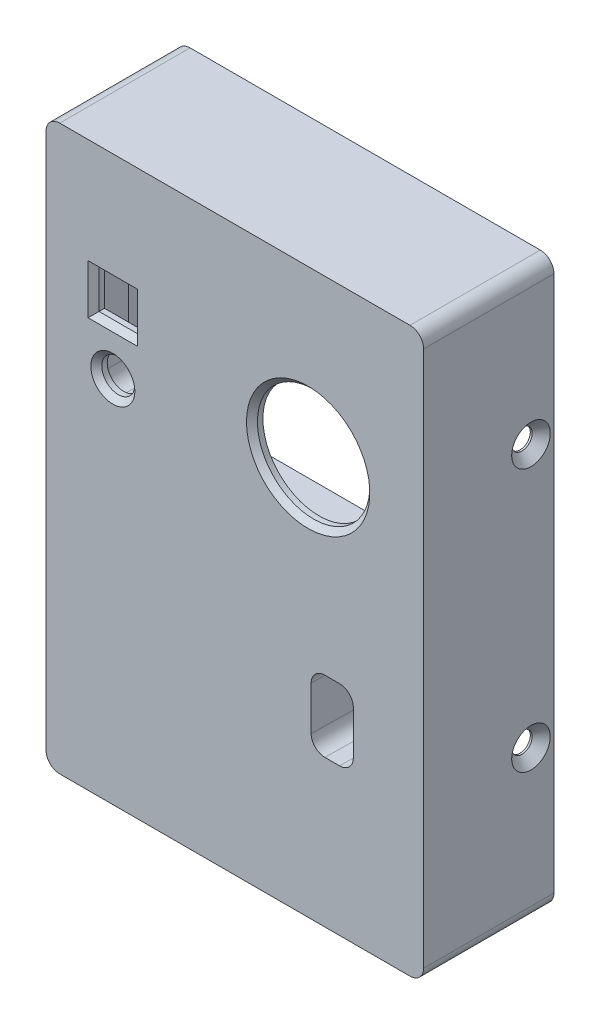
SolidWorks part; units mm, degrees
ref_plane "Front Plane" through (0, 0, 0) normal (0, 0, 1) x (1, 0, 0)
ref_plane "Top Plane" through (0, 0, 0) normal (0, 1, 0) x (1, 0, 0)
ref_plane "Right Plane" through (0, 0, 0) normal (1, 0, 0) x (0, 0, -1)
sketch "Sketch2" plane through (0, 0, 0) normal (0, 0, 1) x (1, 0, 0)
  line L5 (-34.5, -73.3) -> (34.5, -73.3)
  line L6 (-34.5, -73.3) -> (-34.5, 29.7)
  line L7 (-34.5, 29.7) -> (34.5, 29.7)
  line L8 (34.5, -73.3) -> (34.5, 29.7)
extrude "Boss-Extrude1" add sketch "Sketch2" along normal blind 2
sketch "Sketch3" plane through (0, 0, 0) normal (0, 0, -1) x (-1, 0, 0)
  line L1 (34.5, 29.7) -> (-34.5, 29.7)
  line L2 (34.5, 29.7) -> (34.5, -73.3)
  line L3 (34.5, -73.3) -> (-34.5, -73.3)
  line L4 (-34.5, 29.7) -> (-34.5, -73.3)
  line L12 (32.5, -71.3) -> (32.5, 27.7)
  line L13 (32.5, 27.7) -> (-32.5, 27.7)
  line L14 (-32.5, 27.7) -> (-32.5, -71.3)
  line L15 (-32.5, -71.3) -> (32.5, -71.3)
  line L16 (32.5, -71.3) -> (32.5, 27.7)
  line L17 (32.5, 27.7) -> (-32.5, 27.7)
  line L18 (-32.5, 27.7) -> (-32.5, -71.3)
  line L19 (-32.5, -71.3) -> (32.5, -71.3)
  dimension "D1" = 2
extrude "Boss-Extrude2" add sketch "Sketch3" along normal up to surface (21.816 mm away)
sketch "Sketch4" plane through (0, 0, 0) normal (0, 0, -1) x (-1, 0, 0)
  line L0 (26.2, -13.3) -> (18.3635, -13.3) construction
  line L1 (15.8263, -13.3) -> (18.3635, -13.3) construction
  line L2 (15.8263, -13.3) -> (13.1504, -13.3) construction
  line L3 (10.0494, -13.3) -> (13.1504, -13.3) construction
  line L4 (10.0494, -13.3) -> (-0.8511, -13.3) construction
  line L5 (-3.379, -13.3) -> (-0.8511, -13.3) construction
  line L6 (-3.379, -13.3) -> (-11.0624, -13.3) construction
  line L7 (-13.1307, -13.3) -> (-11.0624, -13.3) construction
  line L8 (-13.1307, -13.3) -> (-21.9, -13.3) construction
  line L9 (-26.2, -8.9391) -> (-26.2, -8.1901) construction
  line L10 (-26.2, -6.895) -> (-26.2, -8.1901) construction
  line L11 (-26.2, -6.895) -> (-26.2, -2.3887) construction
  line L12 (-26.2, -1.2629) -> (-26.2, -2.3887) construction
  line L13 (-26.2, -1.2629) -> (-26.2, 3.2404) construction
  line L14 (-26.2, 8) -> (-26.2, 3.2404) construction
  line L15 (-21.9, 12.3) -> (-13.1307, 12.3) construction
  line L16 (-11.0624, 12.3) -> (-13.1307, 12.3) construction
  line L17 (-11.0624, 12.3) -> (-3.379, 12.3) construction
  line L18 (-0.8511, 12.3) -> (-3.379, 12.3) construction
  line L19 (-0.8511, 12.3) -> (10.0494, 12.3) construction
  line L20 (13.1504, 12.3) -> (10.0494, 12.3) construction
  line L21 (13.1504, 12.3) -> (15.8263, 12.3) construction
  line L22 (18.3635, 12.3) -> (15.8263, 12.3) construction
  line L23 (18.3635, 12.3) -> (26.2, 12.3) construction
  line L24 (29, 9.5) -> (29, 8.1768) construction
  line L25 (29, 3.2404) -> (29, 8.1768) construction
  line L26 (29, 3.2404) -> (29, -1.2629) construction
  line L27 (29, -2.3887) -> (29, -1.2629) construction
  line L28 (29, -2.3887) -> (29, -6.895) construction
  line L29 (29, -8.1901) -> (29, -6.895) construction
  line L30 (29, -8.1901) -> (29, -8.9391) construction
  line L31 (29, -10.5) -> (29, -8.9391) construction
  line L32 (26.2, -13.3) -> (18.3635, -13.3) construction
  line L33 (15.8263, -13.3) -> (18.3635, -13.3) construction
  line L34 (15.8263, -13.3) -> (13.1504, -13.3) construction
  line L35 (10.0494, -13.3) -> (13.1504, -13.3) construction
  line L36 (10.0494, -13.3) -> (-0.8511, -13.3) construction
  line L37 (-3.379, -13.3) -> (-0.8511, -13.3) construction
  line L38 (-3.379, -13.3) -> (-11.0624, -13.3) construction
  line L39 (-13.1307, -13.3) -> (-11.0624, -13.3) construction
  line L40 (-13.1307, -13.3) -> (-21.9, -13.3) construction
  line L41 (-26.2, -8.9391) -> (-26.2, -8.1901) construction
  line L42 (-26.2, -6.895) -> (-26.2, -8.1901) construction
  line L43 (-26.2, -6.895) -> (-26.2, -2.3887) construction
  line L44 (-26.2, -1.2629) -> (-26.2, -2.3887) construction
  line L45 (-26.2, -1.2629) -> (-26.2, 3.2404) construction
  line L46 (-26.2, 8) -> (-26.2, 3.2404) construction
  line L47 (-21.9, 12.3) -> (-13.1307, 12.3) construction
  line L48 (-11.0624, 12.3) -> (-13.1307, 12.3) construction
  line L49 (-11.0624, 12.3) -> (-3.379, 12.3) construction
  line L50 (-0.8511, 12.3) -> (-3.379, 12.3) construction
  line L51 (-0.8511, 12.3) -> (10.0494, 12.3) construction
  line L52 (13.1504, 12.3) -> (10.0494, 12.3) construction
  line L53 (13.1504, 12.3) -> (15.8263, 12.3) construction
  line L54 (18.3635, 12.3) -> (15.8263, 12.3) construction
  line L55 (18.3635, 12.3) -> (26.2, 12.3) construction
  line L56 (29, 9.5) -> (29, 8.1768) construction
  line L57 (29, 3.2404) -> (29, 8.1768) construction
  line L58 (29, 3.2404) -> (29, -1.2629) construction
  line L59 (29, -2.3887) -> (29, -1.2629) construction
  line L60 (29, -2.3887) -> (29, -6.895) construction
  line L61 (29, -8.1901) -> (29, -6.895) construction
  line L62 (29, -8.1901) -> (29, -8.9391) construction
  line L63 (29, -10.5) -> (29, -8.9391) construction
  line L64 (-26.2, -8.9391) -> (-26.2, -9) construction
  line L65 (-26.2, -8.9391) -> (-26.2, -9) construction
  line L66 (26.2, -13.25) -> (18.3635, -13.25)
  line L67 (15.8263, -13.25) -> (18.3635, -13.25)
  line L68 (15.8263, -13.25) -> (13.1504, -13.25)
  line L69 (10.0494, -13.25) -> (13.1504, -13.25)
  line L70 (10.0494, -13.25) -> (-0.8511, -13.25)
  line L71 (-3.379, -13.25) -> (-0.8511, -13.25)
  line L72 (-3.379, -13.25) -> (-11.0624, -13.25)
  line L73 (-13.1307, -13.25) -> (-11.0624, -13.25)
  line L74 (-13.1307, -13.25) -> (-21.9, -13.25)
  line L75 (-26.15, -8.9391) -> (-26.15, -9)
  line L76 (-26.15, -8.9391) -> (-26.15, -8.1901)
  line L77 (-26.15, -6.895) -> (-26.15, -8.1901)
  line L78 (-26.15, -6.895) -> (-26.15, -2.3887)
  line L79 (-26.15, -1.2629) -> (-26.15, -2.3887)
  line L80 (-26.15, -1.2629) -> (-26.15, 3.2404)
  line L81 (-26.15, 8) -> (-26.15, 3.2404)
  line L82 (-21.9, 12.25) -> (-13.1307, 12.25)
  line L83 (-11.0624, 12.25) -> (-13.1307, 12.25)
  line L84 (-11.0624, 12.25) -> (-3.379, 12.25)
  line L85 (-0.8511, 12.25) -> (-3.379, 12.25)
  line L86 (-0.8511, 12.25) -> (10.0494, 12.25)
  line L87 (13.1504, 12.25) -> (10.0494, 12.25)
  line L88 (13.1504, 12.25) -> (15.8263, 12.25)
  line L89 (18.3635, 12.25) -> (15.8263, 12.25)
  line L90 (18.3635, 12.25) -> (26.2, 12.25)
  line L91 (28.95, 9.5) -> (28.95, 8.1768)
  line L92 (28.95, 3.2404) -> (28.95, 8.1768)
  line L93 (28.95, 3.2404) -> (28.95, -1.2629)
  line L94 (28.95, -2.3887) -> (28.95, -1.2629)
  line L95 (28.95, -2.3887) -> (28.95, -6.895)
  line L96 (28.95, -8.1901) -> (28.95, -6.895)
  line L97 (28.95, -8.1901) -> (28.95, -8.9391)
  line L98 (28.95, -10.5) -> (28.95, -8.9391)
  line L99 (30.45, -10.5) -> (30.45, -8.9391)
  line L100 (30.45, -8.1901) -> (30.45, -8.9391)
  line L101 (30.45, -8.1901) -> (30.45, -6.895)
  line L102 (30.45, -2.3887) -> (30.45, -6.895)
  line L103 (30.45, -2.3887) -> (30.45, -1.2629)
  line L104 (30.45, 3.2404) -> (30.45, -1.2629)
  line L105 (30.45, 3.2404) -> (30.45, 8.1768)
  line L106 (30.45, 9.5) -> (30.45, 8.1768)
  line L107 (18.3635, 13.75) -> (26.2, 13.75)
  line L108 (18.3635, 13.75) -> (15.8263, 13.75)
  line L109 (13.1504, 13.75) -> (15.8263, 13.75)
  line L110 (13.1504, 13.75) -> (10.0494, 13.75)
  line L111 (-0.8511, 13.75) -> (10.0494, 13.75)
  line L112 (-0.8511, 13.75) -> (-3.379, 13.75)
  line L113 (-11.0624, 13.75) -> (-3.379, 13.75)
  line L114 (-11.0624, 13.75) -> (-13.1307, 13.75)
  line L115 (-21.9, 13.75) -> (-13.1307, 13.75)
  line L116 (-27.65, 8) -> (-27.65, 3.2404)
  line L117 (-27.65, -1.2629) -> (-27.65, 3.2404)
  line L118 (-27.65, -1.2629) -> (-27.65, -2.3887)
  line L119 (-27.65, -6.895) -> (-27.65, -2.3887)
  line L120 (-27.65, -6.895) -> (-27.65, -8.1901)
  line L121 (-27.65, -8.9391) -> (-27.65, -8.1901)
  line L122 (-27.65, -8.9391) -> (-27.65, -9)
  line L123 (-13.1307, -14.75) -> (-21.9, -14.75)
  line L124 (-13.1307, -14.75) -> (-11.0624, -14.75)
  line L125 (-3.379, -14.75) -> (-11.0624, -14.75)
  line L126 (-3.379, -14.75) -> (-0.8511, -14.75)
  line L127 (10.0494, -14.75) -> (-0.8511, -14.75)
  line L128 (10.0494, -14.75) -> (13.1504, -14.75)
  line L129 (15.8263, -14.75) -> (13.1504, -14.75)
  line L130 (15.8263, -14.75) -> (18.3635, -14.75)
  line L131 (26.2, -14.75) -> (18.3635, -14.75)
  arc A0 (-25.8255, -10.7551) -> (-21.9, -13.3) centre (-21.9, -9) ccw construction
  arc A1 (-26.2, -9) -> (-25.8255, -10.7551) centre (-21.9, -9) ccw construction
  arc A2 (-21.9, 12.3) -> (-26.1958, 8.19) centre (-21.9, 8) ccw construction
  arc A3 (29, 9.5) -> (26.2, 12.3) centre (26.2, 9.5) ccw construction
  arc A4 (26.2, -13.3) -> (28.9961, -10.6486) centre (26.2, -10.5) ccw construction
  arc A5 (-25.8255, -10.7551) -> (-21.9, -13.3) centre (-21.9, -9) ccw construction
  arc A6 (-26.2, -9) -> (-25.8255, -10.7551) centre (-21.9, -9) ccw construction
  arc A7 (-21.9, 12.3) -> (-26.1958, 8.19) centre (-21.9, 8) ccw construction
  arc A8 (29, 9.5) -> (26.2, 12.3) centre (26.2, 9.5) ccw construction
  arc A9 (26.2, -13.3) -> (28.9961, -10.6486) centre (26.2, -10.5) ccw construction
  arc A10 (28.9961, -10.6486) -> (29, -10.5) centre (26.2, -10.5) ccw construction
  arc A11 (28.9961, -10.6486) -> (29, -10.5) centre (26.2, -10.5) ccw construction
  arc A12 (-26.1958, 8.19) -> (-26.2, 8) centre (-21.9, 8) ccw construction
  arc A13 (-26.1958, 8.19) -> (-26.2, 8) centre (-21.9, 8) ccw construction
  arc A14 (-25.7799, -10.7347) -> (-21.9, -13.25) centre (-21.9, -9) ccw
  arc A15 (-26.15, -9) -> (-25.7799, -10.7347) centre (-21.9, -9) ccw
  arc A16 (-26.1458, 8.1878) -> (-26.15, 8) centre (-21.9, 8) ccw
  arc A17 (-21.9, 12.25) -> (-26.1458, 8.1878) centre (-21.9, 8) ccw
  arc A18 (28.95, 9.5) -> (26.2, 12.25) centre (26.2, 9.5) ccw
  arc A19 (28.9461, -10.6459) -> (28.95, -10.5) centre (26.2, -10.5) ccw
  arc A20 (26.2, -13.25) -> (28.9461, -10.6459) centre (26.2, -10.5) ccw
  arc A21 (30.45, 9.5) -> (26.2, 13.75) centre (26.2, 9.5) ccw
  arc A22 (-21.9, 13.75) -> (-27.6444, 8.2541) centre (-21.9, 8) ccw
  arc A23 (-27.6444, 8.2541) -> (-27.65, 8) centre (-21.9, 8) ccw
  arc A24 (-27.65, -9) -> (-27.1492, -11.347) centre (-21.9, -9) ccw
  arc A25 (-27.1492, -11.347) -> (-21.9, -14.75) centre (-21.9, -9) ccw
  arc A26 (26.2, -14.75) -> (30.444, -10.7255) centre (26.2, -10.5) ccw
  arc A27 (30.444, -10.7255) -> (30.45, -10.5) centre (26.2, -10.5) ccw
  dimension "D1" = 0.05
  dimension "D2" = 1.5
extrude "Boss-Extrude3" add sketch "Sketch4" along normal blind 7.5
sketch "Sketch7" plane through (0, 0, 0) normal (0, 0, -1) x (-1, 0, 0)
  line L2 (25.821, 9.521) -> (18.779, 9.521)
  line L3 (25.821, 9.521) -> (25.821, 2.479)
  line L4 (25.821, 2.479) -> (18.779, 2.479)
  line L5 (18.779, 9.521) -> (18.779, 2.479)
  circle A0 centre (-13.4, -0.5) radius 10.271
  arc A1 (-4.343, -5.3441) -> (-10.2819, 9.2863) centre (-13.4, -0.5) ccw construction
  circle A2 centre (22.3, -5.9) radius 3.021
  arc A3 (22.3, -8.921) -> (22.3, -2.879) centre (22.3, -5.9) ccw construction
extrude "Cut-Extrude1" cut sketch "Sketch7" against normal through all
sketch "Sketch9" plane through (0, 0, 0) normal (0, 0, -1) x (-1, 0, 0)
  line L0 (-32.5, -71.3) -> (32.5, -71.3) construction
  line L1 (-25, -71.3) -> (-21.5, -71.3)
  line L2 (-25, -71.3) -> (-25, -61.3)
  line L3 (-25, -61.3) -> (-21.5, -61.3)
  line L4 (-21.5, -71.3) -> (-21.5, -61.3)
  line L5 (-23, -33.3) -> (-23, -68.3) construction
  line L6 (-23, -68.3) -> (-23, -61.3)
  line L7 (24, -70.3) -> (20.5, -70.3)
  line L9 (-23, -68.3) -> (-21.5, -68.3)
  line L10 (-23, -68.3) -> (22, -68.3) construction
  line L11 (24, -70.3) -> (24, -59.475)
  line L12 (24, -59.475) -> (20.5, -59.475)
  line L13 (20.5, -70.3) -> (20.5, -59.475)
  line L14 (27.075, -59.5) -> (10.475, -59.5) construction
  line L16 (22, -68.3) -> (22, -33.3) construction
  line L17 (20.5, -68.3) -> (22, -68.3)
  line L18 (22, -68.3) -> (22, -59.475)
  line M17 (-32.5, -71.3) -> (32.5, -71.3)
  dimension "D1" = 2
  dimension "D2" = 3.5
  dimension "D3" = 2
  dimension "D4" = 3.5
  dimension "D5" = 10
  dimension "D6" = 2
  dimension "D7" = 0.025
extrude "Boss-Extrude4" add sketch "Sketch9" along normal up to surface (19.69 mm away) contours L17 L18 L12 L13 | L9 L4 L3 region at (22.25, -64.8, 0) region at (-21.25, -63.8875, 0)
extrude "Boss-Extrude5" add sketch "Sketch9<4>" along normal up to surface (21.3 mm away) contours L18 L17 L13 L11 L12 M17 | L9 L3 L2 L4 M17 region at (23.6786, -66.9429, 0) region at (-22.787, -65.4245, 0)
sketch "Sketch9<4>" plane through (0, 0, 0) normal (0, 0, -1) x (-1, 0, 0) same geometry as "Sketch9"
sketch "Sketch10" plane through (0, 0, 0) normal (0, 0, -1) x (-1, 0, 0)
  line L1 (22, -68.3) -> (22, -33.3) construction
  line L2 (20.975, -34.1125) -> (20.975, -34.4125) construction
  line L3 (22, -46.325) -> (24, -46.325)
  line L7 (10.25, -34.1125) -> (10.25, -31.3)
  line L9 (20.95, -34.1125) -> (10.25, -34.1125)
  line L10 (10.25, -34.1125) -> (10.25, -38.2125)
  line L11 (10.25, -38.2125) -> (20.95, -38.2125)
  line L12 (20.95, -38.2125) -> (20.95, -34.1125)
  line L16 (22, -38.2125) -> (20.95, -38.2125)
  line L18 (22, -33.3) -> (-23, -33.3) construction
  line L21 (20.95, -34.1125) -> (20.95, -31.3)
  line L22 (20.95, -31.3) -> (24, -31.3)
  line L24 (22, -46.325) -> (22, -38.2125)
  line L25 (22, -33.3) -> (22, -38.2125)
  line L26 (22, -33.3) -> (20.95, -33.3)
  line L27 (24, -31.3) -> (24, -46.325)
  line L29 (10.25, -31.3) -> (5.25, -31.3)
  line L30 (5.25, -31.3) -> (5.25, -38.2125)
  line L31 (5.25, -38.2125) -> (10.25, -38.2125)
  line L32 (10.25, -33.3) -> (5.25, -33.3)
  line L33 (10.475, -46.3) -> (27.075, -46.3) construction
  line L34 (10.225, -34.4125) -> (10.225, -37.7125) construction
  point P27 (0, 0)
  dimension "D1" = 2
  dimension "D2" = 2
  dimension "D3" = 2
  dimension "D4" = 0.025
  dimension "D5" = 0.025
  dimension "D6" = 0.025
  dimension "D7" = 5
  dimension "D8" = 4.9125
  dimension "D9" = 4.1
extrude "Boss-Extrude6" add sketch "Sketch10" along normal up to surface (15.33 mm away) contours L11 L12 L9 L10 region at (-15.6, -36.1625, 0)
extrude "Boss-Extrude7" add sketch "Sketch10<4>" along normal up to surface (19.69 mm away) contours L25 L26 L21 L12 L16 | L7 L32 L30 L31 L10 region at (-21.475, -35.7562, 0) region at (-7.75, -35.7562, 0)
sketch "Sketch10<4>" plane through (0, 0, 0) normal (0, 0, -1) x (-1, 0, 0) same geometry as "Sketch10"
extrude "Boss-Extrude8" add sketch "Sketch10<6>" along normal up to surface (21.3 mm away) contours L32 L7 L29 L30 | L27 L22 L21 L26 L25 L24 L3 region at (-22.9004, -38.3871, 0) region at (-7.75, -32.3, 0)
sketch "Sketch10<6>" plane through (0, 0, 0) normal (0, 0, -1) x (-1, 0, 0) same geometry as "Sketch10"
sketch "Sketch11" plane through (0, 0, 0) normal (0, 0, -1) x (-1, 0, 0)
  line L0 (-16.63, -39.95) -> (-19.17, -39.95) construction
  line L1 (-14.15, -33.45) -> (-21.65, -33.45)
  line L2 (-14.15, -33.45) -> (-14.15, -46.45)
  line L3 (-14.15, -46.45) -> (-21.65, -46.45)
  line L4 (-21.65, -33.45) -> (-21.65, -46.45)
  line L5 (-17.9, -44.11) -> (-17.9, -35.79) construction
  line L6 (-16.63, -38.9) -> (-16.63, -41) construction
  line L8 (-19.17, -41) -> (-19.17, -38.9) construction
  line L9 (-17.63, -44.11) -> (-18.17, -44.11) construction
  line L10 (-18.17, -35.79) -> (-17.63, -35.79) construction
  point P23 (-17.9, -46.45)
  point P24 (-14.15, -39.95)
  dimension "D1" = 7.5
  dimension "D2" = 13
extrude "Cut-Extrude2" cut sketch "Sketch11" against normal through all
fillet "Fillet2" radius 2.5 4 edges at (34.5, 29.7, -9.908) (34.5, -73.3, -9.908) (-34.5, -73.3, -9.908) (-34.5, 29.7, -9.908)
chamfer "Chamfer1" distance 1 angle 45 6 edges at (-25.321, -5.9, 2) (-22.3, 2.479, 2) (-25.821, 6, 2) (-18.779, 6, 2) (-22.3, 9.521, 2) (3.129, -0.5, 2)
sketch "Sketch12" plane through (0, -73.3, 0) normal (0, -1, 0) x (1, 0, 0)
  line L0 (32, -21.816) -> (-32, -21.816) construction
  line L1 (-23.8601, -21.816) -> (-22.8601, -21.816)
  line L2 (-23.8601, -21.816) -> (-23.8601, -9.908)
  line L3 (-23.8601, -9.908) -> (-22.8601, -9.908)
  line L4 (-22.8601, -21.816) -> (-22.8601, -9.908)
  line L5 (-32, 2) -> (-32, -21.816) construction
  line L6 (-12.8601, -21.816) -> (-11.8601, -21.816)
  line L7 (-12.8601, -21.816) -> (-12.8601, -9.908)
  line L8 (-12.8601, -9.908) -> (-11.8601, -9.908)
  line L9 (-11.8601, -21.816) -> (-11.8601, -9.908)
  point P12 (-32, -9.908)
  dimension "D1" = 1
  dimension "D2" = 1
  dimension "D3" = 10
extrude "Cut-Extrude3" cut sketch "Sketch12" against normal up to next
sketch "Sketch13" plane through (0, 0, 0) normal (0, 0, -1) x (-1, 0, 0)
  line L1 (-14.15, -33.45) -> (-21.65, -33.45)
  line L2 (-14.15, -33.45) -> (-14.15, -46.45)
  line L3 (-14.15, -46.45) -> (-21.65, -46.45)
  line L4 (-21.65, -33.45) -> (-21.65, -46.45)
  line L8 (22, -33.3) -> (-23, -33.3) construction
  line L9 (-25, -47.95) -> (-12.65, -47.95)
  line L10 (-25, -47.95) -> (-25, -31.3)
  line L11 (-25, -31.3) -> (-12.65, -31.3)
  line L12 (-12.65, -47.95) -> (-12.65, -31.3)
  line L13 (-23, -33.3) -> (-23, -68.3) construction
  dimension "D1" = 1.5
  dimension "D2" = 1.5
  dimension "D3" = 2
  dimension "D4" = 2
extrude "Boss-Extrude9" add sketch "Sketch13" along normal offset from surface (14.69 mm away) 5
sketch "Sketch14" plane through (0, 0, -14.69) normal (0, 0, -1) x (-1, 0, 0)
  line L0 (-17.62, -35.355) -> (-18.18, -35.355)
  line L1 (-21.65, -33.45) -> (-14.15, -33.45)
  line L2 (-21.65, -33.45) -> (-21.65, -46.45)
  line L3 (-21.65, -46.45) -> (-14.15, -46.45)
  line L4 (-17.62, -35.48) -> (-18.18, -35.48)
  line L5 (-16.32, -43.12) -> (-16.32, -36.78)
  line L6 (-18.18, -44.42) -> (-17.62, -44.42)
  line L7 (-19.48, -36.78) -> (-19.48, -43.12)
  line L8 (-17.62, -35.48) -> (-18.18, -35.48) construction
  line L9 (-16.32, -43.12) -> (-16.32, -36.78) construction
  line L10 (-18.18, -44.42) -> (-17.62, -44.42) construction
  line L11 (-19.48, -36.78) -> (-19.48, -43.12) construction
  line L12 (-14.15, -33.45) -> (-14.15, -46.45)
  line L13 (-19.605, -36.78) -> (-19.605, -43.12)
  line L14 (-18.18, -44.545) -> (-17.62, -44.545)
  line L15 (-16.195, -43.12) -> (-16.195, -36.78)
  arc A0 (-16.195, -36.78) -> (-17.62, -35.355) centre (-17.62, -36.78) ccw
  arc A1 (-18.18, -35.355) -> (-19.605, -36.78) centre (-18.18, -36.78) ccw
  arc A2 (-19.605, -43.12) -> (-18.18, -44.545) centre (-18.18, -43.12) ccw
  arc A3 (-17.62, -44.545) -> (-16.195, -43.12) centre (-17.62, -43.12) ccw
  arc A4 (-18.18, -35.48) -> (-19.48, -36.78) centre (-18.18, -36.78) ccw
  arc A5 (-16.32, -36.78) -> (-17.62, -35.48) centre (-17.62, -36.78) ccw
  arc A6 (-17.62, -44.42) -> (-16.32, -43.12) centre (-17.62, -43.12) ccw
  arc A7 (-19.48, -43.12) -> (-18.18, -44.42) centre (-18.18, -43.12) ccw
  arc A8 (-18.18, -35.48) -> (-19.48, -36.78) centre (-18.18, -36.78) ccw construction
  arc A9 (-16.32, -36.78) -> (-17.62, -35.48) centre (-17.62, -36.78) ccw construction
  arc A10 (-17.62, -44.42) -> (-16.32, -43.12) centre (-17.62, -43.12) ccw construction
  arc A11 (-19.48, -43.12) -> (-18.18, -44.42) centre (-18.18, -43.12) ccw construction
  line M13 (-14.15, -33.45) -> (-14.15, -46.45)
  line M14 (-14.15, -46.45) -> (-21.65, -46.45)
  line M15 (-21.65, -46.45) -> (-21.65, -33.45)
  line M16 (-21.65, -33.45) -> (-14.15, -33.45)
  dimension "D2" = 0.125
  dimension "D1" = 0
extrude "Boss-Extrude10" add sketch "Sketch14" against normal blind 5.1 contours A11 L11 A8 L8 A9 L9 A10 L10 M13 M16 M15 M14 region at (17.9, -33.6001, -14.69)
draft "Draft1" type of draft neutral plane draft angle 1 faces to draft 1 face at (14.15, -39.95, -3.795) neutral plane through (0, 0, -9.59) neutral plane normal (0, 0, 1) parameters "D1"=1
fillet "Fillet3" radius 2.5 4 edges at (21.65, -46.45, -3.795) (21.65, -33.45, -3.795) (14.0488, -33.45, -3.795) (14.0488, -46.45, -3.795)
sketch "Sketch16" plane through (0, 0, 0) normal (0, 0, -1) x (-1, 0, 0)
  line L0 (24, -70.3) -> (24, -59.475) construction
  line L1 (24, -67.8) -> (28, -67.8)
  line L2 (24, -67.8) -> (24, -71.3)
  line L3 (24, -71.3) -> (28, -71.3)
  line L4 (28, -67.8) -> (28, -71.3)
  line L5 (23.8601, -71.3) -> (32.5, -71.3) construction
  line L6 (26.65, -70.8) -> (26.65, -67.8)
  line L7 (26.5, 22.2) -> (26.5, -70.8) construction
  line L8 (-25, -71.3) -> (-25, -61.3) construction
  line L9 (-25, -67.8) -> (-28, -67.8)
  line L10 (-25, -67.8) -> (-25, -71.3)
  line L11 (-25, -71.3) -> (-28, -71.3)
  line L12 (-28, -67.8) -> (-28, -71.3)
  line L13 (-32.5, -71.3) -> (11.8601, -71.3) construction
  line L14 (-26.5, -70.8) -> (-26.5, 22.2) construction
  line L15 (-26.65, -70.8) -> (-26.65, -67.8)
  line L16 (-26.65, -67.8) -> (-26.65, -70.8)
  line L17 (-28, -70.8) -> (-25, -70.8)
  line L19 (26.5, -70.8) -> (-26.5, -70.8) construction
  line L20 (28, -70.8) -> (24, -70.8)
  line L21 (-26.5, 22.2) -> (26.5, 22.2) construction
  line L22 (28.5, 24.2) -> (24.5, 24.2)
  line L23 (28.5, 24.2) -> (28.5, 20.2)
  line L24 (28.5, 20.2) -> (24.5, 20.2)
  line L25 (24.5, 24.2) -> (24.5, 20.2)
  line L26 (26.65, 20.2) -> (26.65, 22.35)
  line L27 (-24.5, 24.2) -> (-28.5, 24.2)
  line L28 (-24.5, 24.2) -> (-24.5, 20.2)
  line L29 (-24.5, 20.2) -> (-28.5, 20.2)
  line L30 (-28.5, 24.2) -> (-28.5, 20.2)
  line L31 (26.65, 22.35) -> (24.5, 22.35)
  line L32 (-24.5, 22.35) -> (-26.65, 22.35)
  line L33 (-26.65, 22.35) -> (-26.65, 20.2)
  line M18 (-21.5, -71.3) -> (32.5, -71.3)
  line M22 (-32.5, -71.3) -> (-25, -71.3)
  line M23 (-25, -71.3) -> (-25, -61.3)
  line M26 (24, -59.475) -> (24, -70.3)
  dimension "D1" = 1.5
  dimension "D2" = 1.5
  dimension "D3" = 4
  dimension "D4" = 4
  dimension "D5" = 2
  dimension "D6" = 2
  dimension "D7" = 4
  dimension "D8" = 4
  dimension "D9" = 2
  dimension "D10" = 2
  dimension "D12" = 0.15
  dimension "D13" = 0.15
  dimension "D15" = 0.15
  dimension "D16" = 0.15
  dimension "D17" = 0.15
  dimension "D18" = 0.15
extrude "Boss-Extrude12" add sketch "Sketch16" along normal up to surface (22.8 mm away) contours L26 L31 L25 L24 | L32 L33 L29 L28 | L15 L10 L9 | L1 L2 M26 region at (-25.325, -69.3, 0) region at (25.825, -69.3, 0) region at (-25.575, 21.275, 0) region at (25.575, 21.275, 0)
extrude "Boss-Extrude13" add sketch "Sketch16<4>" along normal up to surface (23.816 mm away) contours L31 L26 L24 L23 L22 L25 | L33 L32 L28 L27 L30 L29 | L15 L9 L12 M22 M23 | L6 L3 L4 L1 region at (-27.325, -69.3, 0) region at (27.325, -69.3, 0) region at (-26.8758, 22.5758, 0) region at (26.8758, 22.5758, 0)
sketch "Sketch16<4>" plane through (0, 0, 0) normal (0, 0, -1) x (-1, 0, 0) same geometry as "Sketch16"
extrude "Boss-Extrude14" add sketch "Sketch16<5>" along normal up to surface (21.816 mm away) contours L17 L12 M22 M23 | L4 L20 L2 M18 region at (-26, -71.05, 0) region at (26.5, -71.05, 0) up to face at (-4.465, -34.425, -21.816)
sketch "Sketch16<5>" plane through (0, 0, 0) normal (0, 0, -1) x (-1, 0, 0) same geometry as "Sketch16"
sketch "Sketch17" plane through (0, -43.8, -23.308) normal (0, -1, 0) x (0, 0, 1)
  line L0 (5.992, 32.25) -> (8.992, 32.25)
  line L1 (5.992, 32.25) -> (8.992, 32.25)
  line L2 (5.692, 32.5) -> (5.692, 33.8958)
  line L3 (1.492, 32.5) -> (23.308, 32.5) construction
  line L4 (5.692, 33.8958) -> (9.042, 32.5)
  line L5 (9.042, 32.5) -> (5.692, 32.5)
  line L7 (1.492, 32.25) -> (1.492, 29.25)
  line L8 (1.492, 29.25) -> (5.242, 30.25)
  line L9 (5.242, 30.25) -> (8.992, 30.25)
  line L10 (8.992, 30.25) -> (8.992, 32.25)
  line L11 (8.992, 32.25) -> (5.992, 33.5)
  line L12 (5.992, 33.5) -> (5.992, 32.25)
  line L13 (5.992, 32.25) -> (1.492, 32.25)
  line L18 (8.992, 32.25) -> (5.992, 33.5) construction
  line L19 (5.992, 33.5) -> (5.992, 32.25) construction
  dimension "D2" = 0.3
  dimension "D3" = 0.25
  dimension "D1" = 0
extrude "Cut-Extrude4" cut sketch "Sketch17" against normal mid plane 10.3 contours L4 L5 L2
sketch "Sketch18" plane through (0, 0.2, -23.308) normal (0, 1, 0) x (0, 0, -1)
  line L3 (-5.692, 32.5) -> (-5.692, 33.8958)
  line L4 (-9.042, 32.5) -> (-5.692, 32.5)
  line L5 (-5.692, 33.8958) -> (-9.042, 32.5)
  line L6 (-5.692, 32.5) -> (-5.692, 33.8958)
  line L7 (-9.042, 32.5) -> (-5.692, 32.5)
  line L8 (-5.692, 33.8958) -> (-9.042, 32.5)
  dimension "D1" = 0
extrude "Cut-Extrude5" cut sketch "Sketch18" against normal mid plane 10.3
sketch "Sketch19" plane through (34.5, 0, 0) normal (1, 0, 0) x (0, 0, -1)
  circle A0 centre (17.616, -45.7) radius 1.875 construction
  circle A1 centre (17.616, 2.3) radius 1.875 construction
  circle A2 centre (17.616, -45.7) radius 1.875
  circle A3 centre (17.616, 2.3) radius 1.875
extrude "Cut-Extrude6" cut sketch "Sketch19" against normal up to surface (2 mm away) up to face at (32.5, -21.8, -10.908)
chamfer "Chamfer5" distance 1.65 angle 45 2 edges at (34.5, -43.825, -17.616) (34.5, 4.175, -17.616)
sketch "Sketch20" plane through (0, 0, -21.816) normal (0, 0, -1) x (-1, 0, 0)
  line L0 (7.3355, -71.3) -> (7.3355, -72.05)
  line L1 (-25, -71.3) -> (11.8601, -71.3) construction
  line L2 (7.3355, -72.05) -> (-8.15, -72.05)
  line L3 (-8.15, -72.05) -> (-8.15, -71.3)
  line L4 (-8.15, -71.3) -> (7.3355, -71.3)
  dimension "D1" = 0.75
extrude "Cut-Extrude7" cut sketch "Sketch20" against normal blind 3
sketch "Sketch22" plane through (0, 0, -14.69) normal (0, 0, -1) x (-1, 0, 0)
  line L2 (-16, -31.3) -> (-25, -31.3)
  line L3 (-25, -31.3) -> (-25, -40.3)
  line L4 (-25, -47.95) -> (-25, -31.3) construction
  line L5 (-25, -40.3) -> (-21.5, -40.3)
  line L6 (-21.5, -40.3) -> (-21.5, -34.8)
  line L7 (-21.5, -34.8) -> (-16, -34.8)
  line L8 (-16, -34.8) -> (-16, -31.3)
  line L10 (-23, -33.3) -> (-23, -40.3)
  line L11 (-23, -33.3) -> (-23, -68.3) construction
  line L12 (-23, -33.3) -> (-16, -33.3)
  line L13 (22, -33.3) -> (-23, -33.3) construction
  line M7 (-12.65, -31.3) -> (-25, -31.3)
  line M8 (-25, -31.3) -> (-25, -47.95)
  dimension "D1" = 7
  dimension "D2" = 7
  dimension "D3" = 1.5
  dimension "D4" = 1.5
extrude "Boss-Extrude15" add sketch "Sketch22" along normal up to surface (5 mm away) contours L12 L10 L5 L6 L7 L8 region at (16.099, -34.05, -14.69)
extrude "Boss-Extrude16" add sketch "Sketch22<4>" along normal up to surface (6.61 mm away) contours L10 L12 L8 L5 M7 M8 region at (16.1273, -32.3, -14.69)
sketch "Sketch22<4>" plane through (0, 0, -14.69) normal (0, 0, -1) x (-1, 0, 0) same geometry as "Sketch22"
sketch "Sketch23" plane through (0, 0, -19.69) normal (0, 0, -1) x (-1, 0, 0)
  line L0 (-23, -33.3) -> (-23, -40.3) construction
  line L1 (-21.5, -34.8) -> (-23, -34.8)
  line L2 (-21.5, -34.8) -> (-21.5, -36.8)
  line L3 (-21.5, -36.8) -> (-23, -36.8)
  line L4 (-23, -34.8) -> (-23, -36.8)
  dimension "D1" = 2
extrude "Cut-Extrude8" cut sketch "Sketch23" against normal blind 1
